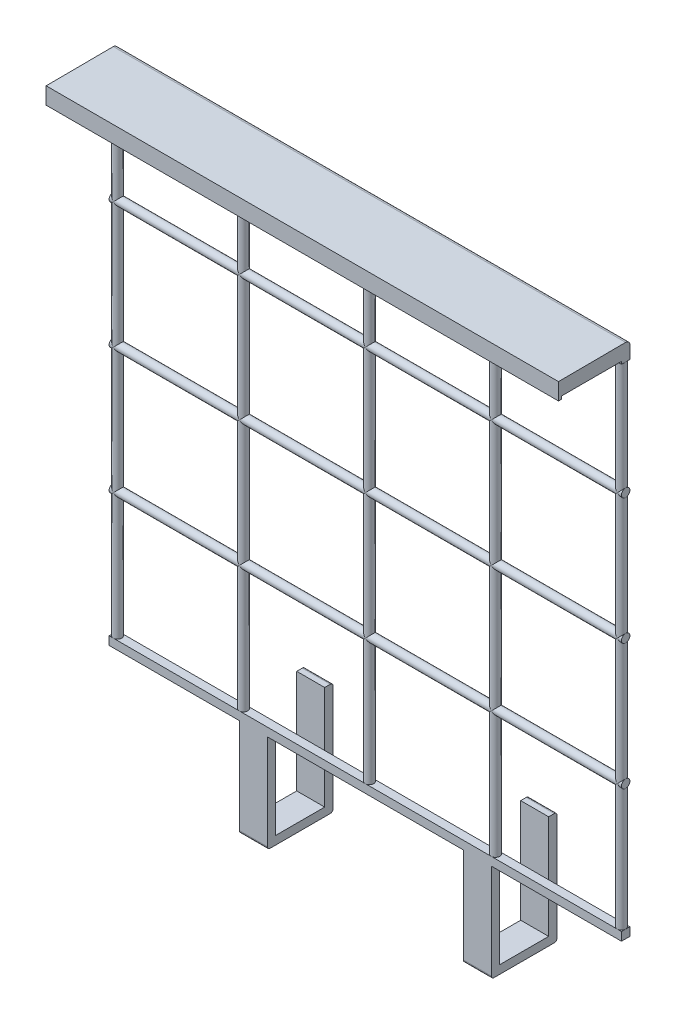
SolidWorks part; units mm, degrees
ref_plane "Front Plane" through (0, 0, 0) normal (0, 0, 1) x (1, 0, 0)
ref_plane "Top Plane" through (0, 0, 0) normal (0, 1, 0) x (1, 0, 0)
ref_plane "Right Plane" through (0, 0, 0) normal (1, 0, 0) x (0, 0, -1)
sketch "Sketch1" plane through (0, 0, 0) normal (0, 0, 1) x (1, 0, 0)
  line L0 (0, 0) -> (180, 0)
  line L1 (0, 0) -> (0, 180)
  line L2 (0, 90) -> (180, 90)
  line L3 (0, 135) -> (180, 135)
  line L4 (180, 0) -> (180, 180)
  line L5 (0, 45) -> (180, 45)
  line L6 (0, 180) -> (180, 180)
  line L7 (45, 0) -> (45, 180)
  line L8 (90, 0) -> (90, 180)
  line L9 (135, 0) -> (135, 180)
  point P16 (0, 180)
  point P18 (90, 0)
  point P19 (0, 0)
  point P20 (0, 180)
  dimension "D1" = 180
  dimension "D2" = 45
  dimension "D3" = 45
  dimension "D4" = 180
  dimension "D5" = 45
  dimension "D6" = 45
sketch "Sketch3" plane through (0, 0, 0) normal (0, 1, 0) x (1, 0, 0)
  line L0 (0, 0) -> (180, 0) construction
  line L1 (0, 0) -> (180, 0) construction
  circle A0 centre (0, 0) radius 1.5
  circle A1 centre (90, 0) radius 1.5
  circle A2 centre (45, 0) radius 1.5
  circle A3 centre (135, 0) radius 1.5
  circle A4 centre (180, 0) radius 1.5
  dimension "D1" = 3
  dimension "D2" = 3
  dimension "D3" = 3
  dimension "D4" = 3
  dimension "D5" = 3
  dimension "D6" = 45
  dimension "D7" = 45
  dimension "D8" = 45
extrude "Boss-Extrude1" add sketch "Sketch3" along normal blind 180 contours A2 | A1 | A4 | A3 | A0 region at (90, 0, 0) region at (45, 0, 0) region at (135, 0, 0) region at (180, 0, 0)
sketch "Sketch4" plane through (0, 0, 0) normal (0, 1, 0) x (1, 0, 0)
  line L0 (0, 1.5) -> (180, 1.5)
  line L2 (180, -1.5) -> (0, -1.5)
  line L4 (181.5, 0) -> (181.5, 1.5)
  line L5 (181.5, 1.5) -> (180, 1.5)
  line L6 (180, -1.5) -> (181.5, -1.5)
  line L7 (181.5, -1.5) -> (181.5, 0)
  line L8 (0, 1.5) -> (-1.5, 1.5)
  line L9 (-1.5, 1.5) -> (-1.5, 0)
  line L10 (-1.5, 0) -> (-1.5, -1.5)
  line L11 (-1.5, -1.5) -> (0, -1.5)
  circle A0 centre (0, 0) radius 1.5 construction
  circle A1 centre (180, 0) radius 1.5 construction
  dimension "D1" = 183
  dimension "D2" = 1.5
  dimension "D3" = 1.5
  dimension "D4" = 1.5
extrude "Boss-Extrude2" add sketch "Sketch4" against normal blind 3 contours L0 L5 L4 L7 L6 L2 L11 L10 L9 L8
sketch "Sketch6" plane through (0, 0, 0) normal (1, 0, 0) x (0, 0, -1)
  line L0 (0, 0) -> (0, 180) construction
  line L2 (1.5, 180) -> (-1.5, 180) construction
  circle A0 centre (0, 90) radius 1.5
  circle A1 centre (0, 180) radius 1.5
  circle A2 centre (0, 135) radius 1.5
  circle A3 centre (0, 45) radius 1.5
  dimension "D1" = 3
  dimension "D2" = 3
  dimension "D3" = 3
  dimension "D4" = 45
  dimension "D5" = 3
  dimension "D6" = 45
extrude "Boss-Extrude3" add sketch "Sketch6" along normal through all and the other way blind 1.5 contours A2 | A0 | A3 | A1
sketch "Sketch7" plane through (0, 0, 1.5) normal (0, 0, 1) x (1, 0, 0)
  line L0 (45, -3) -> (45, -38)
  line L1 (-1.5, -3) -> (181.5, -3) construction
  line L2 (45, -38) -> (55, -38)
  line L3 (55, -38) -> (55, -3)
  line L4 (0, 0) -> (0, 180) construction
  line L5 (45, -3) -> (55, -3)
  dimension "D1" = 35
  dimension "D2" = 10
  dimension "D3" = 45
extrude "Boss-Extrude4" add sketch "Sketch7" against normal blind 3 contours L5 L3 L2 L0
sketch "Sketch8" plane through (55, 0, 0) normal (1, 0, 0) x (0, 0, -1)
  line L0 (1.5, -38) -> (22, -38)
  line L1 (1.5, -38) -> (1.5, -35)
  line L2 (22, -38) -> (22, 2)
  line L3 (22, 2) -> (19, 2)
  line L4 (19, 2) -> (19, -35)
  line L5 (19, -35) -> (1.5, -35)
  line L6 (1.5, -38) -> (1.5, -3) construction
  dimension "D1" = 20.5
  dimension "D2" = 40
  dimension "D3" = 3
  dimension "D4" = 3
extrude "Boss-Extrude5" add sketch "Sketch8" against normal blind 10 contours L1 L5 L4 L3 L2 L0
fillet "Fillet2" radius 1 3 edges at (50, 2, -22) (50, -38, 1.5) (50, -38, -22)
ref_plane "Plane1" through (90, 0, 0) normal (1, 0, 0) x (0, 0, -1)
mirror "Mirror1" about plane through (90, 0, 0) normal (1, 0, 0) of "Fillet2", "Boss-Extrude5", "Boss-Extrude4"
sketch "Sketch9" plane through (181.5, 0, 0) normal (1, 0, 0) x (0, 0, -1)
  line L0 (0, 181.5) -> (-24, 181.3672)
  line L1 (-24, 181.3672) -> (-24, 175.3672)
  line L2 (-24, 175.3672) -> (-23, 175.3672)
  line L3 (-23, 175.3672) -> (-23, 179.3672)
  line L4 (-23, 179.3672) -> (0, 179.3672)
  line L5 (0, 0) -> (0, 180) construction
  line L7 (0, 179.3672) -> (0, 181.5)
  circle A1 centre (0, 180) radius 1.5 construction
  dimension "D1" = 24
  dimension "D2" = 6
  dimension "D3" = 1
  dimension "D4" = 4
  dimension "D6" = 1.5
extrude "Boss-Extrude6" add sketch "Sketch9" against normal blind 183 contours L7 L0 L1 L2 L3 L4
sketch "Sketch11" plane through (181.5, 0, 0) normal (1, 0, 0) x (0, 0, -1)
  line L0 (-1.5, 181.4917) -> (1.5, 180)
  line L1 (-0.0166, 181.4999) -> (-24, 181.3672) construction
  line L2 (1.5, 180) -> (1.5, 175.4472)
  line L3 (1.5, 135) -> (1.5, 180) construction
  line L4 (1.5, 175.4472) -> (-1.5, 175.4472)
  line L5 (-1.5, 179.3672) -> (-1.5, 135) construction
  line L6 (-1.5, 175.4472) -> (-1.5, 181.4917)
extrude "Boss-Extrude7" add sketch "Sketch11" against normal blind 183
sketch "Sketch12" plane through (181.5, 0, 0) normal (1, 0, 0) x (0, 0, -1)
  line L0 (-23, 179.3672) -> (-23, 176.3672)
  line L1 (-23, 175.3672) -> (-23, 179.3672) construction
  line L2 (-23, 176.3672) -> (-1.5, 176.3672)
  line L3 (-1.5, 179.3672) -> (-1.5, 175.4472) construction
  line L4 (-1.5, 176.3672) -> (-1.5, 179.3672)
  line L5 (-1.5, 179.3672) -> (-23, 179.3672)
  line M8 (-23, 175.3672) -> (-23, 179.3672)
  line M9 (-23, 179.3672) -> (-1.5, 179.3672)
  line M10 (-1.5, 179.3672) -> (-1.5, 175.4472)
  dimension "D1" = 3
extrude "Boss-Extrude8" add sketch "Sketch12" against normal blind 1 contours L2 M8 M10 M9 | L5 L0 L2 L4 region at (181.5, 177.8672, 12.25)
mirror "Mirror2" about plane through (90, 0, 0) normal (1, 0, 0) of "Boss-Extrude8"
